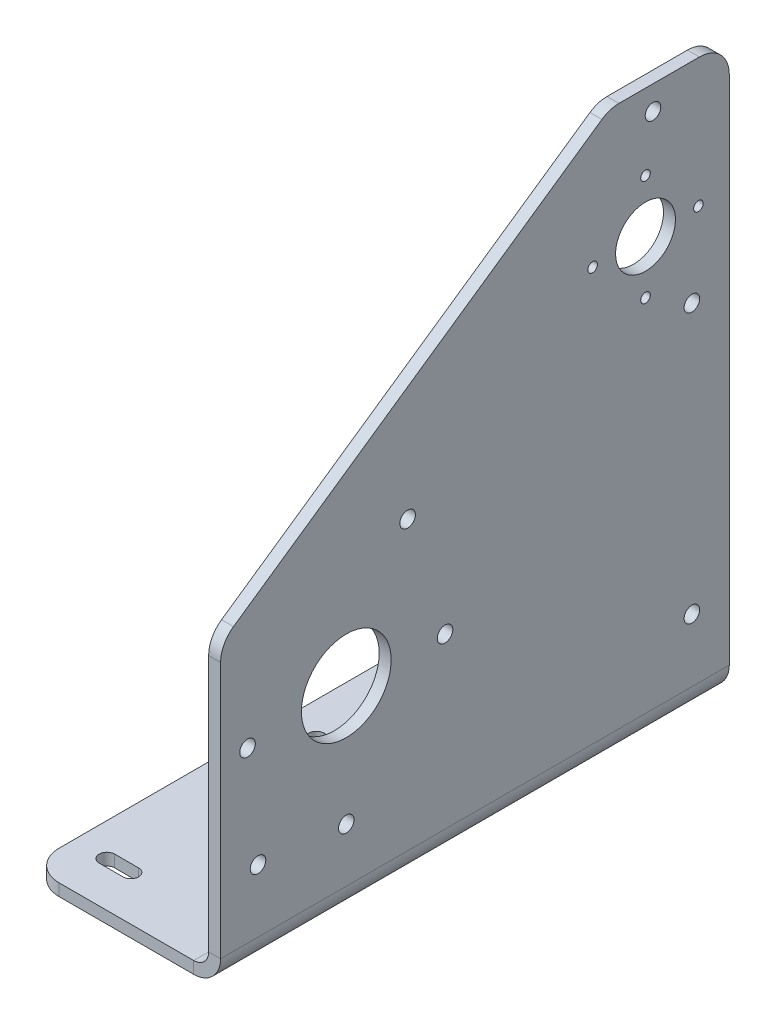
SolidWorks part; units mm, degrees
note: The reader was unsure of these and kept them because the rebuilt part matched: thickness of "Base-Flange1", "Edge-Flange1", "Sheet-Metal1", "Sheet-Metal2", "Sheet-Metal7", "Sheet-Metal8", "Sheet-Metal15", "Sheet-Metal16", "Sheet-Metal18", "Sheet-Metal19", "Sheet-Metal20"; flange length of "Edge-Flange1".
material "5052-H32"
ref_plane "Front Plane" through (0, 0, 0) normal (0, 0, 1) x (1, 0, 0)
ref_plane "Top Plane" through (0, 0, 0) normal (0, 1, 0) x (1, 0, 0)
ref_plane "Right Plane" through (0, 0, 0) normal (1, 0, 0) x (0, 0, -1)
sketch "Sketch1" plane through (0, 0, 0) normal (0, 1, 0) x (1, 0, 0)
  line L1 (-30, -85) -> (30, -85)
  line L2 (-30, -85) -> (-30, 85)
  line L3 (-30, 85) -> (30, 85)
  line L4 (30, -85) -> (30, 85)
  line L5 (-30, -85) -> (30, 85) construction
  line L6 (-30, 85) -> (30, -85) construction
  point P0 (0, 0)
  dimension "D1" = 170
  dimension "D2" = 60
base flange "Base-Flange1" sketch "Sketch1" thickness 4 reverse thickness direction no parameters "D1"=5
edge flange "Edge-Flange1" sketch "Sketch19" flange angle 90 flange length 190 flange position material outside bend radius 5 thickness 4 relief rectangular parameters "D1"=0.7366, "D6"=10
bend "EdgeBend3" bend radius 5 bend angle 90 parameters "D5"=1
sketch "Sketch19" plane through (30, 0, 0) normal (1, 0, 0) x (0, 0, -1)
  line L0 (-85, 0) -> (85, 0) construction
  line L1 (-85, 0) -> (85, 0)
  line L2 (-85, 0) -> (-85, 186)
  line L3 (-85, 186) -> (85, 186)
  line L4 (85, 186) -> (85, 0)
sketch "Sketch15" plane through (34, 0, 0) normal (1, 0, 0) x (0, 0, -1)
  line L2 (-85, 186) -> (-85, 5) construction
  line L3 (85, -4) -> (-85, -4) construction
  circle A0 centre (-43, 63) radius 15
  circle A1 centre (57, 143) radius 10
  dimension "D1" = 30
  dimension "D2" = 20
  dimension "D3" = 80
  dimension "D4" = 42
  dimension "D5" = 67
  dimension "D6" = 100
extrude "Cut-Extrude4" cut sketch "Sketch15" against normal blind 10 normal cut yes
sketch "Sketch16" plane through (34, 0, 0) normal (1, 0, 0) x (0, 0, -1)
  line L5 (-85, 186) -> (-85, 96)
  line L6 (-85, 186) -> (-85, 5) construction
  line L7 (-85, 96) -> (45, 186)
  line L8 (85, 186) -> (-85, 186) construction
  line L9 (45, 186) -> (-85, 186)
  dimension "D1" = 130
  dimension "D2" = 90
extrude "Cut-Extrude5" cut sketch "Sketch16" against normal blind 10 normal cut yes
sketch "Sketch31" plane through (30, 0, 0) normal (-1, 0, 0) x (0, 0, 1)
  line L0 (43, 23) -> (43, 63) construction
  circle A0 centre (76, 61.5) radius 2.6
  circle A1 centre (10, 61.5) radius 2.6
  circle A2 centre (43, 23) radius 2.6
  point P6 (43, 63)
  dimension "D4" = 5.2
  dimension "D1" = 66
  dimension "D2" = 40
  dimension "D3" = 33
  dimension "D5" = 1.5
extrude "Cut-Extrude9" cut sketch "Sketch31" against normal blind 7 normal cut yes
fillet "Fillet1" radius 10 5 edges at (32, 186, -85) (32, 186, -45) (32, 96, 85) (-30, -2, -85) (-30, -2, 85)
sketch "Sketch32" plane through (30, 0, 0) normal (-1, 0, 0) x (0, 0, 1)
  line L0 (-74.6777, 143) -> (-57, 160.6777) construction
  line L5 (-57, 160.6777) -> (-39.3223, 143) construction
  line L6 (-39.3223, 143) -> (-57, 125.3223) construction
  line L7 (-57, 125.3223) -> (-74.6777, 143) construction
  line L8 (-74.6777, 143) -> (-39.3223, 143) construction
  line L9 (-57, 160.6777) -> (-57, 125.3223) construction
  circle A4 centre (-74.6777, 143) radius 1.6
  circle A5 centre (-57, 125.3223) radius 1.6
  circle A6 centre (-39.3223, 143) radius 1.6
  circle A7 centre (-57, 160.6777) radius 1.6
  point P14 (-57, 143)
  dimension "D2" = 3.2
  dimension "D1" = 25
extrude "Cut-Extrude10" cut sketch "Sketch32" against normal blind 10 normal cut yes
hole_wizard "Ø1.0mm Dowel Hole2" positions "Sketch35" profile "Sketch36" hole size "Ø1.0" standard "ANSI Metric"
sketch "Sketch35" plane through (34, 0, 0) normal (1, 0, 0) x (0, 0, -1)
  line L2 (85, -4) -> (-85, -4) construction
  line L4 (75, -4) -> (-75, -4) construction
  point P0 (-72.5, 26)
  point P2 (72.5, 26)
  point P4 (72.5, 116)
  point P6 (-22.5, 101)
  point P25 (0, -4)
  point P26 (59.5, 178)
  dimension "D1" = 145
  dimension "D2" = 30
  dimension "D3" = 72.5
  dimension "D4" = 90
  dimension "D5" = 95
  dimension "D6" = 15
  dimension "D7" = 13
  dimension "D8" = 62
sketch "Sketch36" plane through (34, 26, 72.5) normal (0, 1, 0) x (0, 0, -1)
  line L0 (0, 0) -> (0, 13.5922)
  line L1 (0, 13.5922) -> (2.6, 12.03)
  line L2 (2.6, 12.03) -> (2.6, 0)
  line L5 (2.6, 0) -> (0, 0)
  line L10 (0, 13.5922) -> (-2.6, 12.03) construction
  line L11 (0, -6.35) -> (0, 107.95) construction
  dimension "Hole Dia." = 5.2
  dimension "Hole Depth" = 12.03
  dimension "Drill Angle" = 118
hole_wizard "Ø1.0mm Dowel Hole3" positions "Sketch39" profile "Sketch38" hole size "Ø1.0" standard "ANSI Metric"
sketch "Sketch39" plane through (0, 0, 0) normal (0, 1, 0) x (1, 0, 0)
  line L0 (-30, 75) -> (-30, -75) construction
  point P0 (-15, 70)
  point P2 (-15, 0)
  point P4 (-15, -70)
  point P10 (-30, 0)
  dimension "D1" = 140
  dimension "D2" = 70
  dimension "D3" = 15
sketch "Sketch38" plane through (-15, 0, -70) normal (1, 0, 0) x (0, 0, 1)
  line L0 (0, 0) -> (0, 13.5922)
  line L1 (0, 13.5922) -> (2.6, 12.03)
  line L2 (2.6, 12.03) -> (2.6, 0)
  line L5 (2.6, 0) -> (0, 0)
  line L10 (0, 13.5922) -> (-2.6, 12.03) construction
  line L11 (0, -6.35) -> (0, 107.95) construction
  dimension "Hole Dia." = 5.2
  dimension "Hole Depth" = 12.03
  dimension "Drill Angle" = 118
sketch "Sketch40" plane through (0, 0, 0) normal (0, 1, 0) x (1, 0, 0)
  line L1 (-19, -72.6) -> (-11, -72.6)
  line L2 (-19, -72.6) -> (-19, -67.4) construction
  line L3 (-19, -67.4) -> (-11, -67.4)
  line L4 (-11, -72.6) -> (-11, -67.4) construction
  line L5 (-19, -72.6) -> (-11, -67.4) construction
  line L6 (-19, -67.4) -> (-11, -72.6) construction
  line L7 (-19, -2.6) -> (-11, -2.6)
  line L8 (-19, -2.6) -> (-19, 2.6) construction
  line L9 (-19, 2.6) -> (-11, 2.6)
  line L10 (-11, -2.6) -> (-11, 2.6) construction
  line L11 (-19, -2.6) -> (-11, 2.6) construction
  line L12 (-19, 2.6) -> (-11, -2.6) construction
  line L13 (-19, 67.4) -> (-11, 67.4)
  line L14 (-19, 67.4) -> (-19, 72.6) construction
  line L15 (-19, 72.6) -> (-11, 72.6)
  line L16 (-11, 67.4) -> (-11, 72.6) construction
  line L17 (-19, 67.4) -> (-11, 72.6) construction
  line L18 (-19, 72.6) -> (-11, 67.4) construction
  circle A0 centre (-15, 70) radius 2.6 construction
  circle A1 centre (-15, 0) radius 2.6 construction
  circle A2 centre (-15, -70) radius 2.6 construction
  arc A3 (-11, 72.6) -> (-11, 67.4) centre (-11, 70) cw
  arc A4 (-19, 72.6) -> (-19, 67.4) centre (-19, 70) ccw
  arc A5 (-19, 2.6) -> (-19, -2.6) centre (-19, 0) ccw
  arc A6 (-11, 2.6) -> (-11, -2.6) centre (-11, 0) cw
  arc A7 (-11, -67.4) -> (-11, -72.6) centre (-11, -70) cw
  arc A8 (-19, -67.4) -> (-19, -72.6) centre (-19, -70) ccw
  point P0 (-15, -70)
  point P6 (-15, 0)
  point P12 (-15, 70)
  dimension "D1" = 8
  dimension "D2" = 8
  dimension "D3" = 8
extrude "Cut-Extrude11" cut sketch "Sketch40" against normal blind 10 normal cut yes
sketch "Bend-Lines1" [suppressed] plane through (0, 0, 0) normal (0, 1, 0) x (1, 0, 0)
sketch "Bounding-Box1" [suppressed] plane through (0, 0, 0) normal (0, 1, 0) x (1, 0, 0)
sheet metal parameters "Sheet-Metal1" thickness 4 parameters "D1"=3, "D7"=3
flat pattern "Flat-Pattern1" [suppressed]
sketch "Bend-Lines2" plane through (0, 0, 0) normal (0, 1, 0) x (1, 0, 0)
sketch3d "Bounding-Box2" [suppressed]
  line L0 (7.5, -25, 0) -> (7.5, 25, 0) construction
  line L1 (-7.5, -25, 0) -> (-7.5, 25, 0) construction
  line L2 (7.5, -25, 0) -> (-7.5, -25, 0) construction
  line L3 (7.5, 25, 0) -> (-7.5, 25, 0) construction
sheet metal parameters "Sheet-Metal2" thickness 4 parameters "D1"=3, "D7"=2
flat pattern "Flat-Pattern1"
sketch "Bend-Lines2" plane through (0, 0, 0) normal (0, 1, 0) x (1, 0, 0)
  line L2 (7.6416, -70) -> (7.6416, 70) construction
  line L3 (7.6416, -70) -> (7.6416, 70) construction
  point P0 (-17.6416, 70)
  point P1 (-17.6416, -70)
sketch3d "Bounding-Box2" [suppressed]
  line L0 (135.7832, 70, 0) -> (-7.5, 70, 0) construction
  line L1 (135.7832, -70, 0) -> (-7.5, -70, 0) construction
  line L2 (135.7832, 70, 0) -> (135.7832, -70, 0) construction
  line L3 (-7.5, 70, 0) -> (-7.5, -70, 0) construction
bend of the flat pattern "Flatten-<EdgeBend3>1"
sheet metal parameters "Sheet-Metal7" thickness 4 parameters "D1"=3, "D7"=2
flat pattern "Flat-Pattern1"
sketch "Bend-Lines2" plane through (0, 0, 0) normal (0, 1, 0) x (1, 0, 0)
  line L2 (7.6416, -70) -> (7.6416, 70) construction
  line L3 (7.6416, -70) -> (7.6416, 70) construction
sketch3d "Bounding-Box2" [suppressed]
  line L0 (135.7832, 70, 0) -> (-7.5, 70, 0) construction
  line L1 (135.7832, -70, 0) -> (-7.5, -70, 0) construction
  line L2 (135.7832, 70, 0) -> (135.7832, -70, 0) construction
  line L3 (-7.5, 70, 0) -> (-7.5, -70, 0) construction
bend of the flat pattern "Flatten-<EdgeBend3>2"
sheet metal parameters "Sheet-Metal8" thickness 4 parameters "D1"=3, "D7"=2
flat pattern "Flat-Pattern1"
sketch "Bend-Lines2" plane through (0, 0, 0) normal (0, 1, 0) x (1, 0, 0)
  line L2 (7.6416, -70) -> (7.6416, 70) construction
  line L3 (7.6416, -70) -> (7.6416, 70) construction
sketch3d "Bounding-Box2" [suppressed]
  line L0 (135.7832, 70, 0) -> (-7.5, 70, 0) construction
  line L1 (135.7832, -70, 0) -> (-7.5, -70, 0) construction
  line L2 (135.7832, 70, 0) -> (135.7832, -70, 0) construction
  line L3 (-7.5, 70, 0) -> (-7.5, -70, 0) construction
bend of the flat pattern "Flatten-<EdgeBend3>3"
sheet metal parameters "Sheet-Metal15" thickness 4 parameters "D1"=3, "D7"=2
flat pattern "Flat-Pattern1" [suppressed]
sketch "Bend-Lines2" plane through (0, 0, 0) normal (0, 1, 0) x (1, 0, 0)
  line L0 (-17.5343, 70) -> (-17.5343, -70) construction
  line L1 (-17.5343, 70) -> (-17.5343, -70) construction
  line L2 (20.5343, -70) -> (20.5343, 70) construction
  line L3 (20.5343, -70) -> (20.5343, 70) construction
  line L4 (-42.6029, 70) -> (-42.6029, -70) construction
  line L5 (-42.6029, 70) -> (-42.6029, -70) construction
sketch3d "Bounding-Box2" [suppressed]
  line L0 (-60.1372, 70, 0) -> (198.0686, 70, 0) construction
  line L1 (-60.1372, -70, 0) -> (198.0686, -70, 0) construction
  line L2 (-60.1372, 70, 0) -> (-60.1372, -70, 0) construction
  line L3 (198.0686, 70, 0) -> (198.0686, -70, 0) construction
bend of the flat pattern "Flatten-<EdgeBend3>3"
sketch "Sketch31-1" plane through (21.0686, 0, 0) normal (0, 1, 0) x (0, 0, 1)
  line L0 (30, 24) -> (30, 64) construction
  circle A0 centre (63, 62.5) radius 2.6
  circle A1 centre (-3, 62.5) radius 2.6
  circle A2 centre (30, 24) radius 2.6
  dimension "D4" = 5.2
  dimension "D1" = 66
  dimension "D2" = 40
  dimension "D3" = 33
  dimension "D5" = 1.5
sheet metal parameters "Sheet-Metal16" thickness 4 parameters "D1"=3, "D7"=2
flat pattern "Flat-Pattern1" [suppressed]
sketch "Bend-Lines2" plane through (0, 0, 0) normal (0, 1, 0) x (1, 0, 0)
  line L0 (-17.5343, 70) -> (-17.5343, -70) construction
  line L1 (-17.5343, 70) -> (-17.5343, -70) construction
  line L2 (20.5343, -70) -> (20.5343, 70) construction
  line L3 (20.5343, -70) -> (20.5343, 70) construction
  line L4 (-42.6029, 70) -> (-42.6029, -70) construction
  line L5 (-42.6029, 70) -> (-42.6029, -70) construction
sketch3d "Bounding-Box2" [suppressed]
  line L0 (-60.1372, 70, 0) -> (198.0686, 70, 0) construction
  line L1 (-60.1372, -70, 0) -> (198.0686, -70, 0) construction
  line L2 (-60.1372, 70, 0) -> (-60.1372, -70, 0) construction
  line L3 (198.0686, 70, 0) -> (198.0686, -70, 0) construction
bend of the flat pattern "Flatten-<EdgeBend3>3"
sketch "Sketch31-1" plane through (21.0686, 0, 0) normal (0, 1, 0) x (0, 0, 1)
  line L0 (30, 24) -> (30, 64) construction
  circle A0 centre (63, 62.5) radius 2.6
  circle A1 centre (-3, 62.5) radius 2.6
  circle A2 centre (30, 24) radius 2.6
  dimension "D4" = 5.2
  dimension "D1" = 66
  dimension "D2" = 40
  dimension "D3" = 33
  dimension "D5" = 1.5
sheet metal parameters "Sheet-Metal18" thickness 4 parameters "D1"=3, "D7"=2
flat pattern "Flat-Pattern1" [suppressed]
sketch "Bend-Lines2" plane through (0, 0, 0) normal (0, 1, 0) x (1, 0, 0)
  line L2 (30.5343, -85) -> (30.5343, 85) construction
  line L3 (30.5343, -85) -> (30.5343, 85) construction
sketch3d "Bounding-Box2" [suppressed]
  line L0 (-30, 85, 0) -> (218.0686, 85, 0) construction
  line L1 (-30, -85, 0) -> (218.0686, -85, 0) construction
  line L2 (-30, 85, 0) -> (-30, -85, 0) construction
  line L3 (218.0686, 85, 0) -> (218.0686, -85, 0) construction
bend of the flat pattern "Flatten-<EdgeBend3>3"
sketch "Sketch31-1" plane through (31.0686, 0, 0) normal (0, 1, 0) x (0, 0, 1)
  line L0 (43, 24) -> (43, 64) construction
  circle A0 centre (76, 62.5) radius 2.6
  circle A1 centre (10, 62.5) radius 2.6
  circle A2 centre (43, 24) radius 2.6
  point P6 (43, 64)
  dimension "D4" = 5.2
  dimension "D1" = 66
  dimension "D2" = 40
  dimension "D3" = 33
  dimension "D5" = 1.5
sheet metal parameters "Sheet-Metal19" thickness 4 parameters "D1"=3, "D7"=2
flat pattern "Flat-Pattern1" [suppressed]
sketch "Bend-Lines2" plane through (0, 0, 0) normal (0, 1, 0) x (1, 0, 0)
  line L2 (30.4978, -85) -> (30.4978, 85) construction
  line L3 (30.4978, -85) -> (30.4978, 85) construction
sketch3d "Bounding-Box2" [suppressed]
  line L0 (-30, 85, 0) -> (216.9956, 85, 0) construction
  line L1 (-30, -85, 0) -> (216.9956, -85, 0) construction
  line L2 (-30, 85, 0) -> (-30, -85, 0) construction
  line L3 (216.9956, 85, 0) -> (216.9956, -85, 0) construction
bend of the flat pattern "Flatten-<EdgeBend3>3"
sketch "Sketch31-1" plane through (30.9956, 0, 0) normal (0, 1, 0) x (0, 0, 1)
  line L0 (43, 23) -> (43, 63) construction
  circle A0 centre (76, 61.5) radius 2.6
  circle A1 centre (10, 61.5) radius 2.6
  circle A2 centre (43, 23) radius 2.6
  point P6 (43, 63)
  dimension "D4" = 5.2
  dimension "D1" = 66
  dimension "D2" = 40
  dimension "D3" = 33
  dimension "D5" = 1.5
sheet metal parameters "Sheet-Metal20" thickness 4 parameters "D1"=3, "D7"=2
flat pattern "Flat-Pattern1" [suppressed]
sketch "Bend-Lines2" plane through (0, 0, 0) normal (0, 1, 0) x (1, 0, 0)
  line L2 (30.4978, -85) -> (30.4978, 85) construction
  line L3 (30.4978, -85) -> (30.4978, 85) construction
sketch3d "Bounding-Box2" [suppressed]
  line L0 (-30, 85, 0) -> (216.9956, 85, 0) construction
  line L1 (-30, -85, 0) -> (216.9956, -85, 0) construction
  line L2 (-30, 85, 0) -> (-30, -85, 0) construction
  line L3 (216.9956, 85, 0) -> (216.9956, -85, 0) construction
bend of the flat pattern "Flatten-<EdgeBend3>3"
sketch "Sketch31-1" plane through (30.9956, 0, 0) normal (0, 1, 0) x (0, 0, 1)
  line L0 (43, 23) -> (43, 63) construction
  circle A0 centre (76, 61.5) radius 2.6
  circle A1 centre (10, 61.5) radius 2.6
  circle A2 centre (43, 23) radius 2.6
  point P6 (43, 63)
  dimension "D4" = 5.2
  dimension "D1" = 66
  dimension "D2" = 40
  dimension "D3" = 33
  dimension "D5" = 1.5
